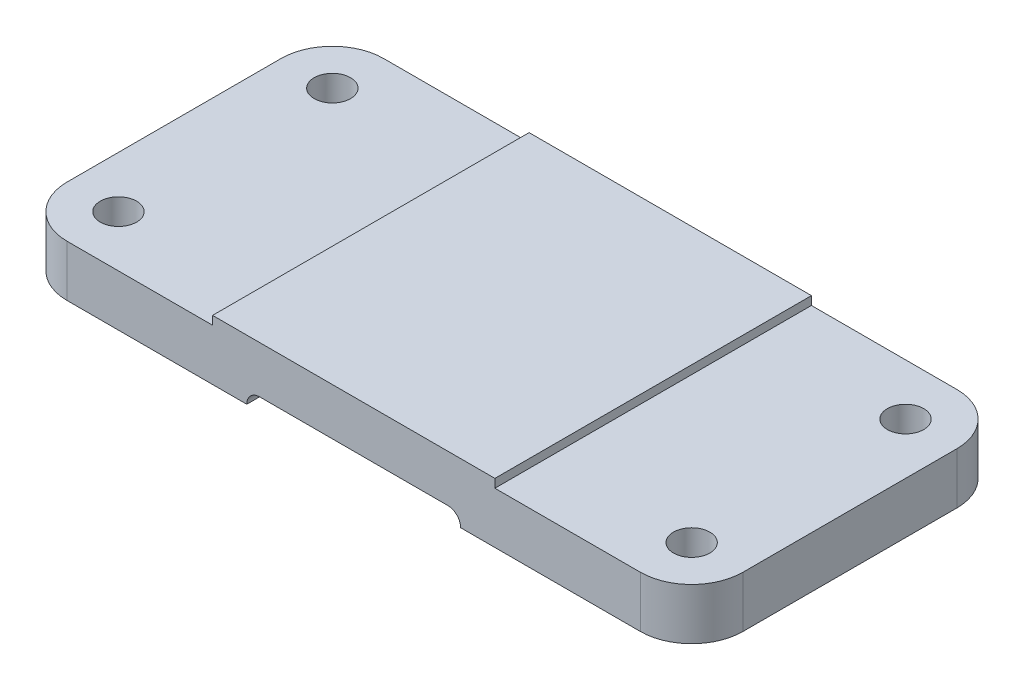
SolidWorks part; units mm, degrees
material "Gray Cast Iron"
ref_plane "Front Plane" through (0, 0, 0) normal (0, 0, 1) x (1, 0, 0)
ref_plane "Top Plane" through (0, 0, 0) normal (0, 1, 0) x (1, 0, 0)
ref_plane "Right Plane" through (0, 0, 0) normal (1, 0, 0) x (0, 0, -1)
sketch "Sketch1" plane through (0, 0, 0) normal (0, 0, 1) x (1, 0, 0)
  line L0 (-8.6178, -8.1939) -> (35.3822, -8.1939)
  line L1 (-19.6178, 2.8061) -> (46.3822, 2.8061)
  line L2 (-19.6178, 2.8061) -> (-19.6178, 0.8061)
  line L4 (46.3822, 2.8061) -> (46.3822, 0.8061)
  line L5 (-19.6178, 0.8061) -> (-65.6178, 0.8061)
  line L7 (-11.6178, -11.1939) -> (-65.6178, -11.1939)
  line L8 (-65.6178, 0.8061) -> (-65.6178, -11.1939)
  line L9 (46.3822, 0.8061) -> (92.3822, 0.8061)
  line L11 (38.3822, -11.1939) -> (92.3822, -11.1939)
  line L12 (92.3822, 0.8061) -> (92.3822, -11.1939)
  arc A0 (38.3822, -11.1939) -> (35.3822, -8.1939) centre (35.3822, -11.1939) ccw
  arc A1 (-8.6178, -8.1939) -> (-11.6178, -11.1939) centre (-8.6178, -11.1939) ccw
  dimension "D1" = 3
  dimension "D2" = 14
  dimension "D3" = 12
  dimension "D4" = 12
  dimension "D5" = 14
  dimension "D6" = 46
  dimension "D7" = 46
  dimension "D8" = 158
  dimension "D9" = 54
  dimension "D10" = 54
extrude "Boss-Extrude1" add sketch "Sketch1" along normal blind 74
fillet "Fillet1" radius 12 4 edges at (92.3822, -5.1939, 0) (92.3822, -5.1939, 74) (-65.6178, -5.1939, 74) (-65.6178, -5.1939, 0)
sketch "Sketch6" plane through (0, 0.8061, 0) normal (0, 1, 0) x (1, 0, 0)
  line L0 (80.3822, -109.8533) -> (80.3822, 21.0306) construction
  line L1 (122.7289, -62) -> (-108.2091, -62) construction
  line L2 (122.0295, -12) -> (-108.9907, -12) construction
  line L3 (-53.6178, -102.5486) -> (-53.6178, 18.3631) construction
  line L4 (46.3822, -74) -> (46.3822, 0) construction
  line L6 (-19.6178, -74) -> (-19.6178, 0) construction
  line L9 (80.3822, -74) -> (46.3822, -74) construction
  circle A0 centre (80.3822, -62) radius 6
  circle A1 centre (80.3822, -12) radius 6
  circle A2 centre (-53.6178, -62) radius 6
  circle A3 centre (-53.6178, -12) radius 6
  dimension "D1" = 12
  dimension "D2" = 12
  dimension "D3" = 12
  dimension "D4" = 12
  dimension "D5" = 34
  dimension "D6" = 34
  dimension "D7" = 50
  dimension "D8" = 12
hole_wizard "M10 Tapped Hole1" positions "3DSketch2" profile "Sketch7" tap size "M10" standard "AS"
sketch3d "3DSketch2"
  point P0 (80.3822, 0.8061, 62)
  point P3 (80.3822, 0.8061, 12)
  point P6 (-53.6178, 0.8061, 12)
  point P9 (-53.6178, 0.8061, 62)
sketch "Sketch7" plane through (80.3822, 0.8061, 62) normal (1, 0, 0) x (0, 0, 1)
  line L0 (0, 0) -> (0, 27.0537)
  line L1 (0, 27.0537) -> (4.25, 24.5)
  line L2 (4.25, 24.5) -> (4.25, 0)
  line L5 (4.25, 0) -> (0, 0)
  line L10 (0, 27.0537) -> (-4.25, 24.5) construction
  line L11 (0, -6.35) -> (0, 107.95) construction
  dimension "Tap Drill Dia." = 8.5
  dimension "Tap Drill Depth" = 24.5
  dimension "Drill Angle" = 118
cosmetic thread "Hole Thread1" parameters "D1"=12, "D2"=10
cosmetic thread "Hole Thread2" parameters "D1"=12, "D2"=10
cosmetic thread "Hole Thread3" parameters "D1"=12, "D2"=10
cosmetic thread "Hole Thread4" parameters "D1"=12, "D2"=10
equation "\"D4@Sketch1\"=\"D3@Sketch1\""
equation "\"D5@Sketch1\"=\"D2@Sketch1\""
